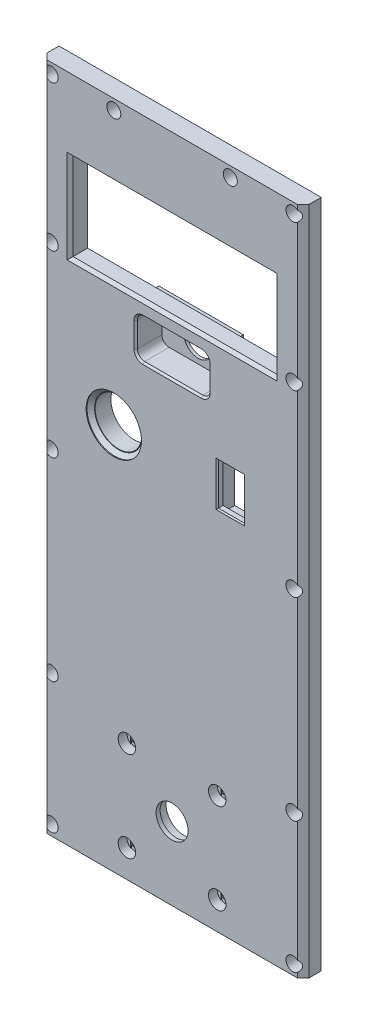
SolidWorks part; units mm, degrees
ref_plane "Front Plane" through (0, 0, 0) normal (0, 0, 1) x (1, 0, 0)
ref_plane "Top Plane" through (0, 0, 0) normal (0, 1, 0) x (1, 0, 0)
ref_plane "Right Plane" through (0, 0, 0) normal (1, 0, 0) x (0, 0, -1)
sketch "Sketch1" plane through (0, 0, 0) normal (0, 0, 1) x (1, 0, 0)
  line L1 (-45, -115) -> (45, -115)
  line L2 (-45, -115) -> (-45, 115)
  line L3 (-45, 115) -> (45, 115)
  line L4 (45, -115) -> (45, 115)
  line L5 (-45, -115) -> (45, 115) construction
  line L6 (-45, 115) -> (45, -115) construction
  line L7 (-38, -108) -> (38, -108)
  line L8 (-38, -108) -> (-38, 108)
  line L9 (-38, 108) -> (38, 108)
  line L10 (38, -108) -> (38, 108)
  line L11 (-38, -108) -> (38, 108) construction
  line L12 (-38, 108) -> (38, -108) construction
  point P0 (0, 0)
  point P6 (0, 0)
  dimension "D1" = 230
  dimension "D2" = 90
  dimension "D3" = 7
  dimension "D4" = 7
extrude "Boss-Extrude1" add sketch "Sketch1" along normal blind 7
sketch "Sketch2" plane through (0, 0, 7) normal (0, 0, 1) x (1, 0, 0)
  line L0 (38, -108) -> (38, 108) construction
  line L1 (-38, -108) -> (38, -108)
  line L2 (-38, -108) -> (-38, -58)
  line L3 (-38, -58) -> (38, -58)
  line L4 (38, -108) -> (38, -58)
  dimension "D1" = 50
extrude "Boss-Extrude2" add sketch "Sketch2" against normal up to surface (7 mm away) up to face at (0, 0, 0)
sketch "Sketch3" plane through (0, 0, 0) normal (0, 0, -1) x (-1, 0, 0)
  line L0 (0, -115) -> (0, -90) construction
  line L1 (45, -115) -> (-45, -115) construction
  circle A0 centre (0, -90) radius 5.5
  dimension "D1" = 11
  dimension "D2" = 25
extrude "Cut-Extrude1" cut sketch "Sketch3" against normal through all
sketch "Sketch4" plane through (0, 0, 0) normal (0, 0, -1) x (-1, 0, 0)
  circle A0 centre (0, -90) radius 6.05
  dimension "D1" = 12.1
extrude "Cut-Extrude2" cut sketch "Sketch4" against normal offset from surface (5.6 mm away) 1.4 up to face at (-5.5, -90, 7)
sketch "Sketch5" plane through (0, 0, 0) normal (0, 0, -1) x (-1, 0, 0)
  circle A0 centre (0, -90) radius 12
  dimension "D1" = 24
extrude "Cut-Extrude3" cut sketch "Sketch5" against normal offset from surface (3 mm away) 2.6 up to face at (-6.05, -90, 5.6)
sketch "Sketch6" plane through (0, 0, 0) normal (0, 0, -1) x (-1, 0, 0)
  line L1 (-15.5, -105.5) -> (15.5, -105.5) construction
  line L2 (-15.5, -105.5) -> (-15.5, -74.5) construction
  line L3 (-15.5, -74.5) -> (15.5, -74.5) construction
  line L4 (15.5, -105.5) -> (15.5, -74.5) construction
  line L5 (-15.5, -105.5) -> (15.5, -74.5) construction
  line L6 (-15.5, -74.5) -> (15.5, -105.5) construction
  circle A0 centre (-15.5, -74.5) radius 1.7
  circle A1 centre (15.5, -74.5) radius 1.7
  circle A2 centre (15.5, -105.5) radius 1.7
  circle A3 centre (-15.5, -105.5) radius 1.7
  point P0 (0, -90)
  dimension "D2" = 3.4
  dimension "D1" = 31
extrude "Cut-Extrude4" cut sketch "Sketch6" against normal through all
sketch "Sketch7" plane through (0, 0, 0) normal (0, 0, -1) x (-1, 0, 0)
  line L1 (-30, -112.5) -> (30, -112.5)
  line L2 (-30, -112.5) -> (-30, -67.5)
  line L3 (-30, -67.5) -> (30, -67.5)
  line L4 (30, -112.5) -> (30, -67.5)
  line L5 (-30, -112.5) -> (30, -67.5) construction
  line L6 (-30, -67.5) -> (30, -112.5) construction
  point P0 (0, -90)
  dimension "D1" = 60
  dimension "D2" = 45
extrude "Cut-Extrude5" cut sketch "Sketch7" against normal blind 1
sketch "Sketch8" plane through (0, 0, 7) normal (0, 0, 1) x (1, 0, 0)
  circle A0 centre (-15.5, -74.5) radius 3
  circle A1 centre (15.5, -74.5) radius 3
  circle A2 centre (15.5, -105.5) radius 3
  circle A3 centre (-15.5, -105.5) radius 3
  dimension "D1" = 6
extrude "Cut-Extrude6" cut sketch "Sketch8" against normal blind 3
sketch "Sketch9" plane through (0, 0, 7) normal (0, 0, 1) x (1, 0, 0)
  line L0 (-45, 115) -> (-45, -115) construction
  line L1 (-41.5, -111.5) -> (41.5, -111.5) construction
  line L2 (-41.5, -111.5) -> (-41.5, 111.5) construction
  line L3 (-41.5, 111.5) -> (41.5, 111.5) construction
  line L4 (41.5, -111.5) -> (41.5, 111.5) construction
  line L5 (-41.5, -111.5) -> (41.5, 111.5) construction
  line L6 (-41.5, 111.5) -> (41.5, -111.5) construction
  line L7 (45, 115) -> (-45, 115) construction
  circle A0 centre (-41.5, 111.5) radius 1.45
  circle A1 centre (41.5, 111.5) radius 1.45
  circle A4 centre (-41.5, -111.5) radius 1.45
  circle A5 centre (41.5, -111.5) radius 1.45
  circle A6 centre (-41.5, 61.5) radius 1.45
  circle A7 centre (41.5, 61.5) radius 1.45
  circle A8 centre (41.5, -66.5) radius 1.45
  circle A9 centre (-41.5, -66.5) radius 1.45
  circle A10 centre (-41.5, 0) radius 1.45
  circle A11 centre (41.5, 0) radius 1.45
  point P0 (0, 0)
  dimension "D3" = 2.9
  dimension "D1" = 3.5
  dimension "D2" = 3.5
  dimension "D4" = 45
  dimension "D5" = 50
extrude "Cut-Extrude7" cut sketch "Sketch9" against normal through all
sketch "Sketch10" plane through (0, 0, 7) normal (0, 0, 1) x (1, 0, 0)
  circle A0 centre (-41.5, 111.5) radius 2.4
  circle A1 centre (41.5, 61.5) radius 2.4
  circle A2 centre (-41.5, 61.5) radius 2.4
  circle A3 centre (41.5, 111.5) radius 2.4
  circle A4 centre (-41.5, -111.5) radius 2.4
  circle A5 centre (41.5, -111.5) radius 2.4
  circle A6 centre (-41.5, -66.5) radius 2.4
  circle A7 centre (41.5, -66.5) radius 2.4
  circle A8 centre (-41.5, 0) radius 2.4
  circle A9 centre (41.5, 0) radius 2.4
  dimension "D1" = 4.8
extrude "Cut-Extrude8" cut sketch "Sketch10" against normal blind 5
chamfer "Chamfer1" distance 2 angle 45 2 edges at (-45, 0, 7) (45, 0, 7)
sketch "Sketch11" plane through (0, 0, 7) normal (0, 0, 1) x (1, 0, 0)
  line L0 (38, -58) -> (38, 108) construction
  line L1 (-38, -58) -> (38, -58)
  line L2 (-38, -58) -> (-38, -36.4)
  line L3 (-38, -36.4) -> (38, -36.4)
  line L4 (38, -58) -> (38, -36.4)
  line L5 (-43, -115) -> (43, -115) construction
  dimension "D1" = 78.6
extrude "Boss-Extrude3" add sketch "Sketch11" against normal up to surface (7 mm away) up to face at (-40.05, 0, 0)
sketch "Sketch12" plane through (0, 0, 7) normal (0, 0, 1) x (1, 0, 0)
  line L0 (-41.5, 111.5) -> (41.5, 111.5) construction
  line L1 (-20, 111.5) -> (20, 111.5) construction
  circle A0 centre (-20, 111.5) radius 1.45
  circle A1 centre (20, 111.5) radius 1.45
  circle A2 centre (-41.5, 111.5) radius 1.45 construction
  point P7 (0, 111.5)
  dimension "D1" = 40
extrude "Cut-Extrude9" cut sketch "Sketch12" against normal through all
sketch "Sketch13" plane through (0, 0, 7) normal (0, 0, 1) x (1, 0, 0)
  circle A0 centre (-20, 111.5) radius 2.4
  circle A1 centre (20, 111.5) radius 2.4
  circle A2 centre (-41.5, 111.5) radius 2.4 construction
extrude "Cut-Extrude10" cut sketch "Sketch13" against normal up to surface (5 mm away) up to face at (-39.1, 111.5, 2)
chamfer "Chamfer2" distance 0.8 angle 45 12 edges at (0, -115, 0) (-45, 0, 0) (0, 115, 0) (45, 0, 0) (38, 35.8, 7) (0, 108, 7) (-38, 35.8, 7) (0, -36.4, 7) (-38, 35.8, 0) (0, 108, 0) (38, 35.8, 0) (0, -36.4, 0)
sketch "Sketch14" plane through (0, 0, 2) normal (0, 0, 1) x (1, 0, 0)
  line L2 (-42.95, -68.4125) -> (-42.95, -64.5875)
  line L4 (-40.05, -68.4125) -> (-40.05, -64.5875)
  line L5 (-42.95, -68.4125) -> (-40.05, -64.5875) construction
  line L6 (-42.95, -64.5875) -> (-40.05, -68.4125) construction
  line L14 (-42.95, -113.4125) -> (-42.95, -109.5875)
  line L16 (-40.05, -113.4125) -> (-40.05, -109.5875)
  line L17 (-42.95, -113.4125) -> (-40.05, -109.5875) construction
  line L18 (-42.95, -109.5875) -> (-40.05, -113.4125) construction
  line L26 (-42.95, 59.5875) -> (-42.95, 63.4125)
  line L28 (-40.05, 59.5875) -> (-40.05, 63.4125)
  line L29 (-42.95, 59.5875) -> (-40.05, 63.4125) construction
  line L30 (-42.95, 63.4125) -> (-40.05, 59.5875) construction
  line L32 (-21.45, 109.5875) -> (-21.45, 113.4125)
  line L34 (-18.55, 109.5875) -> (-18.55, 113.4125)
  line L35 (-21.45, 109.5875) -> (-18.55, 113.4125) construction
  line L36 (-21.45, 113.4125) -> (-18.55, 109.5875) construction
  line L38 (-42.95, 109.5875) -> (-42.95, 113.4125)
  line L40 (-40.05, 109.5875) -> (-40.05, 113.4125)
  line L41 (-42.95, 109.5875) -> (-40.05, 113.4125) construction
  line L42 (-42.95, 113.4125) -> (-40.05, 109.5875) construction
  arc A0 (-43, -68.3735) -> (-43, -64.6265) centre (-41.5, -66.5) ccw construction
  circle A2 centre (-41.5, -111.5) radius 2.4 construction
  circle A4 centre (-41.5, 61.5) radius 2.4 construction
  circle A5 centre (-20, 111.5) radius 2.4 construction
  circle A6 centre (-41.5, 111.5) radius 2.4 construction
  circle A7 centre (-41.5, 111.5) radius 1.45 construction
  circle A8 centre (-20, 111.5) radius 1.45 construction
  circle A9 centre (-41.5, 61.5) radius 1.45 construction
  circle A10 centre (-41.5, -66.5) radius 1.45 construction
  circle A12 centre (-41.5, -111.5) radius 1.45 construction
  arc A16 (-21.45, 109.5875) -> (-18.55, 109.5875) centre (-20, 111.5) ccw
  arc A17 (-40.05, 113.4125) -> (-42.95, 113.4125) centre (-41.5, 111.5) ccw
  arc A18 (-40.05, 63.4125) -> (-42.95, 63.4125) centre (-41.5, 61.5) ccw
  arc A20 (-42.95, -68.4125) -> (-40.05, -68.4125) centre (-41.5, -66.5) ccw
  arc A22 (-40.05, -109.5875) -> (-42.95, -109.5875) centre (-41.5, -111.5) ccw
  arc A23 (-42.95, 109.5875) -> (-40.05, 109.5875) centre (-41.5, 111.5) ccw
  arc A24 (-18.55, 113.4125) -> (-21.45, 113.4125) centre (-20, 111.5) ccw
  arc A25 (-42.95, 59.5875) -> (-40.05, 59.5875) centre (-41.5, 61.5) ccw
  arc A26 (-40.05, -64.5875) -> (-42.95, -64.5875) centre (-41.5, -66.5) ccw
  arc A29 (-42.95, -113.4125) -> (-40.05, -113.4125) centre (-41.5, -111.5) ccw
  point P0 (-41.5, -66.5)
  point P17 (-41.5, -111.5)
  point P33 (-41.5, 61.5)
  point P41 (-20, 111.5)
  point P49 (-41.5, 111.5)
extrude "Cut-Extrude11" cut sketch "Sketch14" against normal blind 0.2
sketch "Sketch15" plane through (0, 0, 1.8) normal (0, 0, 1) x (1, 0, 0)
  line L0 (-40.05, -111.5) -> (-40.05, -109.5875) construction
  line L1 (-42.95, -112.95) -> (-40.05, -112.95)
  line L2 (-42.95, -112.95) -> (-42.95, -110.05)
  line L3 (-42.95, -110.05) -> (-40.05, -110.05)
  line L4 (-40.05, -112.95) -> (-40.05, -110.05)
  line L5 (-42.95, -112.95) -> (-40.05, -110.05) construction
  line L6 (-42.95, -110.05) -> (-40.05, -112.95) construction
  line L7 (-40.05, 61.5) -> (-40.05, 63.4125) construction
  line L8 (-42.95, -67.95) -> (-40.05, -67.95)
  line L9 (-42.95, -67.95) -> (-42.95, -65.05)
  line L10 (-42.95, -65.05) -> (-40.05, -65.05)
  line L11 (-40.05, -67.95) -> (-40.05, -65.05)
  line L12 (-42.95, -67.95) -> (-40.05, -65.05) construction
  line L13 (-42.95, -65.05) -> (-40.05, -67.95) construction
  line L14 (-42.95, 60.05) -> (-40.05, 60.05)
  line L15 (-42.95, 60.05) -> (-42.95, 62.95)
  line L16 (-42.95, 62.95) -> (-40.05, 62.95)
  line L17 (-40.05, 60.05) -> (-40.05, 62.95)
  line L18 (-42.95, 60.05) -> (-40.05, 62.95) construction
  line L19 (-42.95, 62.95) -> (-40.05, 60.05) construction
  line L20 (-40.05, 109.5875) -> (-40.05, 113.4125) construction
  line L21 (-42.95, 110.05) -> (-40.05, 110.05)
  line L22 (-42.95, 110.05) -> (-42.95, 112.95)
  line L23 (-42.95, 112.95) -> (-40.05, 112.95)
  line L24 (-40.05, 110.05) -> (-40.05, 112.95)
  line L25 (-42.95, 110.05) -> (-40.05, 112.95) construction
  line L26 (-42.95, 112.95) -> (-40.05, 110.05) construction
  line L27 (-18.55, 109.5875) -> (-18.55, 113.4125) construction
  line L28 (-21.45, 110.05) -> (-18.55, 110.05)
  line L29 (-21.45, 110.05) -> (-21.45, 112.95)
  line L30 (-21.45, 112.95) -> (-18.55, 112.95)
  line L31 (-18.55, 110.05) -> (-18.55, 112.95)
  line L32 (-21.45, 110.05) -> (-18.55, 112.95) construction
  line L33 (-21.45, 112.95) -> (-18.55, 110.05) construction
  arc A0 (-40.05, -66.5) -> (-42.95, -66.5) centre (-41.5, -66.5) ccw construction
  arc A1 (-40.05, 61.5) -> (-42.95, 61.5) centre (-41.5, 61.5) ccw construction
  arc A2 (-18.55, 111.5) -> (-21.45, 111.5) centre (-20, 111.5) ccw construction
  arc A3 (-40.05, 111.5) -> (-42.95, 111.5) centre (-41.5, 111.5) ccw construction
  point P0 (-41.5, -111.5)
  point P8 (-41.5, -66.5)
  point P17 (-41.5, 61.5)
  point P28 (-41.5, 111.5)
  point P36 (-20, 111.5)
extrude "Cut-Extrude12" cut sketch "Sketch15" against normal blind 0.2
sketch "Sketch16" plane through (0, 0, 4) normal (0, 0, 1) x (1, 0, 0)
  line L2 (-17.2, -76.9718) -> (-17.2, -72.0282)
  line L4 (-13.8, -76.9718) -> (-13.8, -72.0282)
  line L5 (-17.2, -76.9718) -> (-13.8, -72.0282) construction
  line L6 (-17.2, -72.0282) -> (-13.8, -76.9718) construction
  line L8 (-17.2, -107.9718) -> (-17.2, -103.0282)
  line L10 (-13.8, -107.9718) -> (-13.8, -103.0282)
  line L11 (-17.2, -107.9718) -> (-13.8, -103.0282) construction
  line L12 (-17.2, -103.0282) -> (-13.8, -107.9718) construction
  circle A0 centre (-15.5, -74.5) radius 3 construction
  circle A1 centre (-15.5, -105.5) radius 3 construction
  circle A2 centre (-15.5, -105.5) radius 1.7 construction
  circle A3 centre (-15.5, -74.5) radius 1.7 construction
  circle A4 centre (-15.5, -105.5) radius 3 construction
  circle A5 centre (-15.5, -74.5) radius 3 construction
  arc A6 (-13.8, -103.0282) -> (-17.2, -103.0282) centre (-15.5, -105.5) ccw
  arc A7 (-17.2, -76.9718) -> (-13.8, -76.9718) centre (-15.5, -74.5) ccw
  arc A8 (-13.8, -72.0282) -> (-17.2, -72.0282) centre (-15.5, -74.5) ccw
  arc A9 (-17.2, -107.9718) -> (-13.8, -107.9718) centre (-15.5, -105.5) ccw
  point P0 (-15.5, -74.5)
  point P8 (-15.5, -105.5)
extrude "Cut-Extrude13" cut sketch "Sketch16" against normal blind 0.2
sketch "Sketch17" plane through (0, 0, 3.8) normal (0, 0, 1) x (1, 0, 0)
  line L0 (-13.8, -76.9718) -> (-13.8, -72.0282) construction
  line L1 (-17.2, -76.2) -> (-13.8, -76.2)
  line L2 (-17.2, -76.2) -> (-17.2, -72.8)
  line L3 (-17.2, -72.8) -> (-13.8, -72.8)
  line L4 (-13.8, -76.2) -> (-13.8, -72.8)
  line L5 (-17.2, -76.2) -> (-13.8, -72.8) construction
  line L6 (-17.2, -72.8) -> (-13.8, -76.2) construction
  line L7 (-13.8, -107.9718) -> (-13.8, -103.0282) construction
  line L8 (-17.2, -107.2) -> (-13.8, -107.2)
  line L9 (-17.2, -107.2) -> (-17.2, -103.8)
  line L10 (-17.2, -103.8) -> (-13.8, -103.8)
  line L11 (-13.8, -107.2) -> (-13.8, -103.8)
  line L12 (-17.2, -107.2) -> (-13.8, -103.8) construction
  line L13 (-17.2, -103.8) -> (-13.8, -107.2) construction
  arc A0 (-13.8, -105.5) -> (-17.2, -105.5) centre (-15.5, -105.5) ccw construction
  arc A1 (-13.8, -74.5) -> (-17.2, -74.5) centre (-15.5, -74.5) ccw construction
  point P0 (-15.5, -74.5)
  point P8 (-15.5, -105.5)
extrude "Cut-Extrude14" cut sketch "Sketch17" against normal blind 0.2
mirror "Mirror1" about plane through (0, 0, 0) normal (1, 0, 0) of "Cut-Extrude12", "Cut-Extrude13", "Cut-Extrude14", "Cut-Extrude11"
sketch "Sketch18" plane through (0, 0, 7) normal (0, 0, 1) x (1, 0, 0)
  line L0 (38.8, 108.8) -> (38.8, -37.2) construction
  line L1 (-38.8, 108.8) -> (38.8, 108.8)
  line L2 (-38.8, 108.8) -> (-38.8, 70.8)
  line L3 (-38.8, 70.8) -> (38.8, 70.8)
  line L4 (38.8, 108.8) -> (38.8, 70.8)
  dimension "D1" = 38
extrude "Boss-Extrude4" add sketch "Sketch18" against normal up to surface (7 mm away) up to face at (0, 35.8, 0)
chamfer "Chamfer3" distance 0.8 angle 45 1 edges at (0, 70.8, 7)
sketch "Sketch19" plane through (0, 0, 7) normal (0, 0, 1) x (1, 0, 0)
  line L1 (-38.8, 71.6) -> (38.8, 71.6)
  line L2 (-38.8, 71.6) -> (-38.8, -37.2)
  line L3 (-38.8, -37.2) -> (38.8, -37.2)
  line L4 (38.8, 71.6) -> (38.8, -37.2)
extrude "Boss-Extrude5" add sketch "Sketch19" against normal up to surface (7 mm away) up to face at (0, 16.8, 0)
sketch "Sketch20" plane through (0, 0, 2) normal (0, 0, 1) x (1, 0, 0)
  line L2 (-42.95, -1.9125) -> (-42.95, 1.9125)
  line L4 (-40.05, -1.9125) -> (-40.05, 1.9125)
  line L5 (-42.95, -1.9125) -> (-40.05, 1.9125) construction
  line L6 (-42.95, 1.9125) -> (-40.05, -1.9125) construction
  arc A0 (-43, -1.8735) -> (-43, 1.8735) centre (-41.5, 0) ccw construction
  circle A1 centre (-41.5, 0) radius 1.45 construction
  arc A2 (-42.95, -1.9125) -> (-40.05, -1.9125) centre (-41.5, 0) ccw
  arc A3 (-40.05, 1.9125) -> (-42.95, 1.9125) centre (-41.5, 0) ccw
  point P0 (-41.5, 0)
extrude "Cut-Extrude15" cut sketch "Sketch20" against normal blind 0.2
sketch "Sketch21" plane through (0, 0, 1.8) normal (0, 0, 1) x (1, 0, 0)
  line L0 (-40.05, -1.9125) -> (-40.05, 1.9125) construction
  line L1 (-42.95, -1.45) -> (-40.05, -1.45)
  line L2 (-42.95, -1.45) -> (-42.95, 1.45)
  line L3 (-42.95, 1.45) -> (-40.05, 1.45)
  line L4 (-40.05, -1.45) -> (-40.05, 1.45)
  line L5 (-42.95, -1.45) -> (-40.05, 1.45) construction
  line L6 (-42.95, 1.45) -> (-40.05, -1.45) construction
  arc A0 (-40.05, 0) -> (-42.95, 0) centre (-41.5, 0) ccw construction
  point P0 (-41.5, 0)
extrude "Cut-Extrude16" cut sketch "Sketch21" against normal blind 0.2
mirror "Mirror2" about plane through (0, 0, 0) normal (1, 0, 0) of "Cut-Extrude16", "Cut-Extrude15"
sketch "Sketch22" plane through (0, 0, 7) normal (0, 0, 1) x (1, 0, 0)
  line L0 (43, 115) -> (-43, 115) construction
  line L1 (-35, 40) -> (35, 40)
  line L2 (-35, 40) -> (-35, 90)
  line L3 (-35, 90) -> (35, 90)
  line L4 (35, 40) -> (35, 90)
  line L5 (-35, 40) -> (35, 90) construction
  line L6 (-35, 90) -> (35, 40) construction
  point P0 (0, 65)
  dimension "D1" = 25
  dimension "D2" = 70
  dimension "D3" = 50
extrude "Cut-Extrude17" cut sketch "Sketch22" against normal through all
sketch "Sketch23" plane through (0, 0, 7) normal (0, 0, 1) x (1, 0, 0)
  line L0 (-20, 18) -> (20, 18) construction
  line L1 (15.5, 10.75) -> (24.5, 10.75)
  line L2 (15.5, 10.75) -> (15.5, 25.25)
  line L3 (15.5, 25.25) -> (24.5, 25.25)
  line L4 (24.5, 10.75) -> (24.5, 25.25)
  line L5 (15.5, 10.75) -> (24.5, 25.25) construction
  line L6 (15.5, 25.25) -> (24.5, 10.75) construction
  circle A0 centre (-20, 18) radius 8
  point P0 (20, 18)
  point P7 (0, 18)
  dimension "D3" = 16
  dimension "D1" = 9
  dimension "D2" = 14.5
  dimension "D4" = 18
  dimension "D5" = 40
extrude "Cut-Extrude18" cut sketch "Sketch23" against normal through all
sketch "Sketch24" plane through (0, 0, 0) normal (0, 0, -1) x (-1, 0, 0)
  line L0 (-15.5, 25.25) -> (-24.5, 10.75) construction
  line L1 (-24.5, 25.25) -> (-15.5, 25.25) construction
  line L2 (-25.5, 7.75) -> (-14.5, 7.75)
  line L3 (-25.5, 7.75) -> (-25.5, 28.25)
  line L4 (-25.5, 28.25) -> (-14.5, 28.25)
  line L5 (-14.5, 7.75) -> (-14.5, 28.25)
  line L6 (-25.5, 7.75) -> (-14.5, 28.25) construction
  line L7 (-25.5, 28.25) -> (-14.5, 7.75) construction
  line L8 (-15.5, 25.25) -> (-15.5, 10.75) construction
  point P4 (-20, 18)
  dimension "D1" = 3
  dimension "D2" = 1
extrude "Cut-Extrude19" cut sketch "Sketch24" against normal offset from surface (5 mm away) 2 up to face at (20, 18, 7)
sketch "Sketch25" plane through (0, 0, 7) normal (0, 0, 1) x (1, 0, 0)
  circle A0 centre (-20, 18) radius 9.5
  dimension "D1" = 19
extrude "Cut-Extrude20" cut sketch "Sketch25" against normal blind 1.6
chamfer "Chamfer5" distance 1.3 angle 45 1 edges at (-10.5, 18, 5.4)
chamfer "Chamfer6" distance 0.4 angle 45 4 edges at (15.5, 18, 7) (20, 10.75, 7) (24.5, 18, 7) (20, 25.25, 7)
sketch "Sketch26" plane through (0, 0, 0) normal (0, 0, -1) x (-1, 0, 0)
  circle A0 centre (0, -5) radius 1.7
  circle A1 centre (10, -5) radius 1.7
  circle A2 centre (20, -5) radius 1.7
  circle A3 centre (30, -5) radius 1.7
  circle A4 centre (10, -15) radius 1.7
  circle A5 centre (20, -15) radius 1.7
  circle A6 centre (30, -15) radius 1.7
  circle A7 centre (10, -25) radius 1.7
  circle A8 centre (20, -25) radius 1.7
  circle A9 centre (30, -25) radius 1.7
  circle A10 centre (10, -35) radius 1.7
  circle A11 centre (20, -35) radius 1.7
  circle A12 centre (30, -35) radius 1.7
  circle A13 centre (10, -45) radius 1.7
  circle A14 centre (20, -45) radius 1.7
  circle A15 centre (30, -45) radius 1.7
  circle A16 centre (0, -15) radius 1.7
  circle A17 centre (0, -25) radius 1.7
  circle A18 centre (0, -35) radius 1.7
  circle A19 centre (0, -45) radius 1.7
  dimension "D1" = 3.4
  dimension "D2" = 5
  dimension "D3" = 4
  dimension "D4" = 5
extrude "Cut-Extrude21" cut sketch "Sketch26" against normal blind 4
mirror "Mirror3" about plane through (0, 0, 0) normal (1, 0, 0) of "Cut-Extrude21"
sketch "Sketch27" plane through (0, 0, 7) normal (0, 0, 1) x (1, 0, 0)
  line L0 (35, 40) -> (35, 90) construction
  line L1 (-35, 40) -> (35, 40)
  line L2 (-35, 40) -> (-35, 60)
  line L3 (-35, 60) -> (35, 60)
  line L4 (35, 40) -> (35, 60)
  dimension "D1" = 20
extrude "Boss-Extrude6" add sketch "Sketch27" against normal up to surface (7 mm away) up to face at (21.7, -35, 0)
sketch "Sketch28" plane through (0, 0, 7) normal (0, 0, 1) x (1, 0, 0)
  line L0 (35, 60) -> (-35, 60) construction
  line L1 (-12.5, 55) -> (12.5, 55)
  line L2 (-12.5, 55) -> (-12.5, 41.5)
  line L3 (-12.5, 41.5) -> (12.5, 41.5)
  line L4 (12.5, 55) -> (12.5, 41.5)
  point P4 (0, 55)
  dimension "D1" = 25
  dimension "D2" = 13.5
  dimension "D3" = 5
extrude "Cut-Extrude22" cut sketch "Sketch28" against normal through all
sketch "Sketch29" plane through (0, 0, 0) normal (0, 0, -1) x (-1, 0, 0)
  line L1 (-12.5, 55) -> (12.5, 55)
  line L2 (-12.5, 55) -> (-12.5, 41.5)
  line L3 (-12.5, 41.5) -> (12.5, 41.5)
  line L4 (12.5, 55) -> (12.5, 41.5)
  line L5 (-14.5, 57) -> (14.5, 57)
  line L6 (-14.5, 57) -> (-14.5, 39.5)
  line L7 (-14.5, 39.5) -> (14.5, 39.5)
  line L8 (14.5, 57) -> (14.5, 39.5)
  dimension "D1" = 2
  dimension "D2" = 2
  dimension "D3" = 2
  dimension "D4" = 2
extrude "Boss-Extrude9" add sketch "Sketch29" along normal blind 2
sketch "Sketch30" plane through (0, 0, -2) normal (0, 0, -1) x (-1, 0, 0)
  line L1 (-14.5, 57) -> (14.5, 57)
  line L2 (-14.5, 57) -> (-14.5, 39.5)
  line L3 (-14.5, 39.5) -> (14.5, 39.5)
  line L4 (14.5, 57) -> (14.5, 39.5)
extrude "Boss-Extrude10" add sketch "Sketch30" along normal blind 1
sketch "Sketch31" plane through (0, 0, -3) normal (0, 0, -1) x (-1, 0, 0)
  line L0 (14.5, 57) -> (-14.5, 39.5) construction
  circle A0 centre (0, 48.25) radius 5
  dimension "D1" = 10
extrude "Cut-Extrude23" cut sketch "Sketch31" against normal through all
sketch "Sketch32" plane through (12.5, 0, 0) normal (-1, 0, 0) x (0, 0, 1)
  line L0 (-2, 55) -> (-2, 41.5) construction
  line L1 (-2, 50.75) -> (6.4, 50.75)
  line L2 (-2, 50.75) -> (-2, 45.75)
  line L3 (-2, 45.75) -> (6.4, 45.75)
  line L4 (6.4, 50.75) -> (6.4, 45.75)
  line L5 (-3, 39.5) -> (-3, 57) construction
  line L6 (7, 41.5) -> (7, 55) construction
  point P6 (-2, 42.5799)
  point P9 (-3, 48.25)
  point P10 (-2, 48.25)
  dimension "D1" = 0.6
  dimension "D2" = 5
extrude "Cut-Extrude24" cut sketch "Sketch32" against normal blind 6
fillet "Fillet1" radius 2.5 4 edges at (12.5, 41.5, 2.5) (-12.5, 41.5, 2.5) (12.5, 55, 2.5) (-12.5, 55, 2.5)
chamfer "Chamfer7" distance 0.6 angle 45 8 edges at (0, 41.5, 7) (11.7678, 42.2322, 7) (-11.7678, 42.2322, 7) (12.5, 48.25, 7) (-12.5, 48.25, 7) (11.7678, 54.2678, 7) (-11.7678, 54.2678, 7) (0, 55, 7)
chamfer "Chamfer8" distance 1 angle 45 4 edges at (-35, 75, 0) (0, 90, 0) (35, 75, 0) (0, 60, 0)
chamfer "Chamfer9" distance 1 angle 45 4 edges at (0, 90, 7) (-35, 75, 7) (0, 60, 7) (35, 75, 7)
